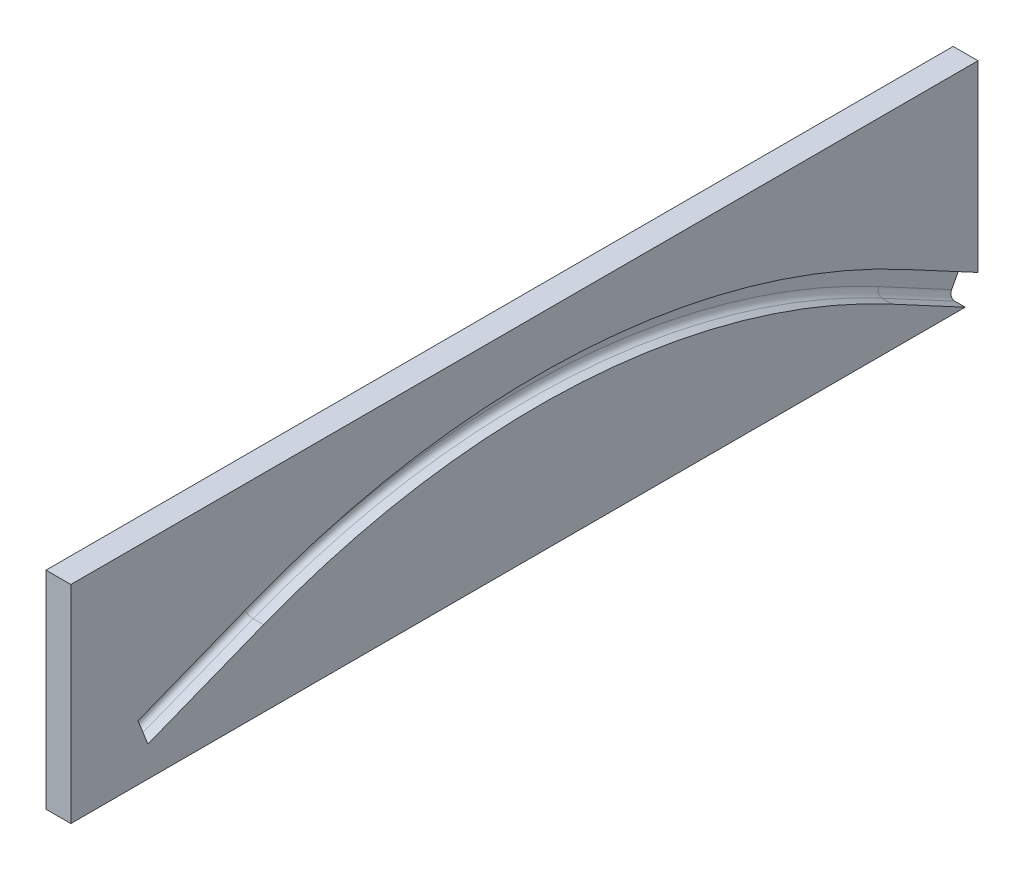
SolidWorks part; units mm, degrees
ref_plane "Plano frontal" through (0, 0, 0) normal (0, 0, 1) x (1, 0, 0)
ref_plane "Plano superior" through (0, 0, 0) normal (0, 1, 0) x (1, 0, 0)
ref_plane "Plano direito" through (0, 0, 0) normal (1, 0, 0) x (0, 0, -1)
sketch "Esboço2" plane through (3.9652, 1.0725, 0.0203) normal (-1, 0, 0) x (0, 0, 1)
  line L0 (-103.1365, 148.9365) -> (112.8201, 148.9365)
  line L1 (112.8201, 148.9365) -> (112.8201, 198.9365)
  line L2 (112.8201, 198.9365) -> (-106.2077, 198.9365)
  line L3 (-106.2077, 198.9365) -> (-106.2077, 154.6651)
  line L4 (94.2122, 156.2676) -> (112.8201, 148.9365) construction
  line L5 (-0.0203, -1.0725) -> (-0.0203, 42.6006) construction
  line L23 (94.2122, 156.2676) -> (96.5948, 162.3152)
  line L24 (-106.2077, 154.6651) -> (-103.1365, 148.9365)
  line L25 (96.5948, 162.3152) -> (68.6829, 173.3118)
  line L26 (66.3003, 167.2642) -> (94.2122, 156.2676)
  line L27 (-88.5811, 164.1152) -> (-106.2077, 154.6651)
  line L28 (-103.1365, 148.9365) -> (-85.5099, 158.3865)
  arc A7 (68.6829, 173.3118) -> (-88.5811, 164.1152) centre (-0.0203, -1.0725) ccw
  arc A8 (66.3003, 167.2642) -> (-85.5099, 158.3865) centre (-0.0203, -1.0725) ccw
  dimension "D3" = 187.43
  dimension "D1" = 49.7
  dimension "D2" = 30
  dimension "D4" = 20
  dimension "D5" = 6.5
  dimension "D6" = 50
  dimension "D7" = 20
extrude "Ressalto-extrusão1" add sketch "Esboço2" along normal blind 2 contours L26 A8 L28 L0 L1 L2 L3 L27 A7 L25 L23 | A8 L26 L23 L25 A7 L27 L24 L28 region at (3.9652, 175.1096, 4.6713) region at (3.9652, 153.8478, -102.8343)
extrude "Ressalto-extrusão2" add sketch "Esboço2<3>" against normal blind 4 contours L26 A8 L28 L0 L1 L2 L3 L27 A7 L25 L23 region at (3.9652, 175.1096, 4.6713)
sketch "Esboço2<3>" plane through (3.9652, 1.0725, 0.0203) normal (-1, 0, 0) x (0, 0, 1) same geometry as "Esboço2"
fillet "Filete1" radius 1.5 6 edges at (3.9652, 154.734, -94.3029) (3.9652, 160.4627, -97.3742) (3.9652, 180.6214, -10.5625) (3.9652, 162.8384, 80.2765) (3.9652, 168.886, 82.6591) (3.9652, 187.1103, -10.942)
